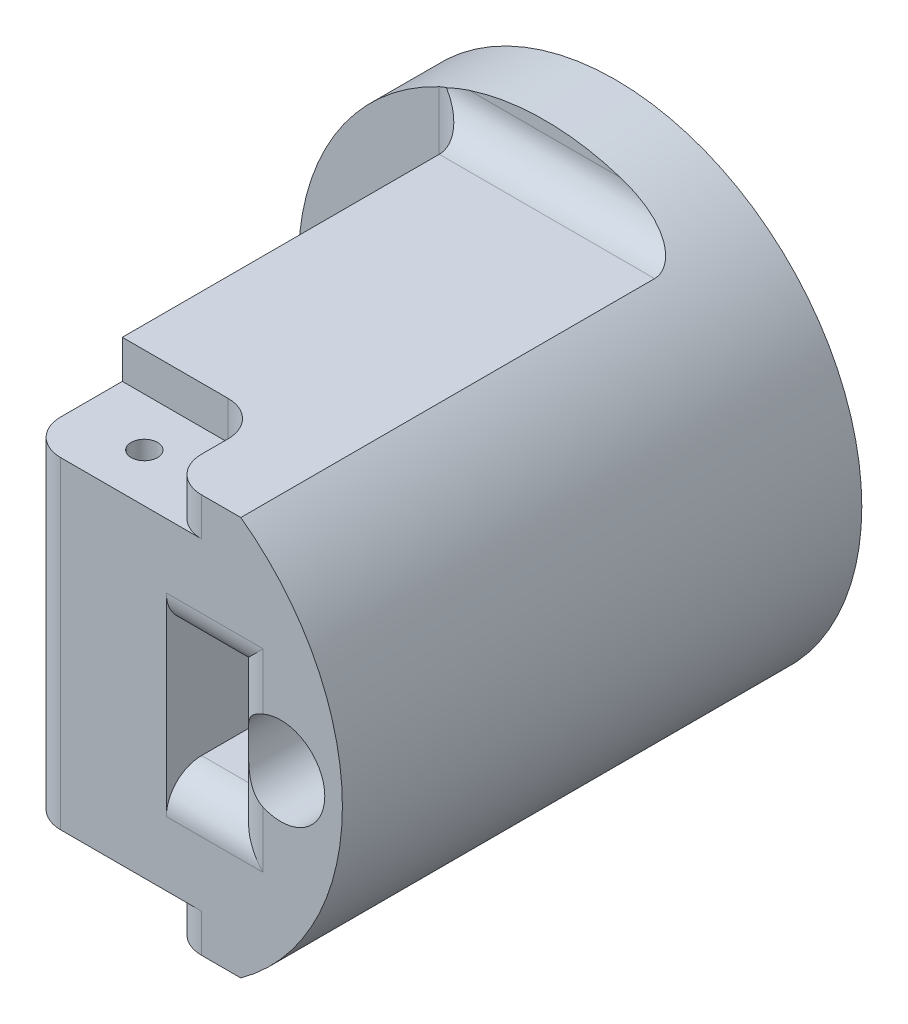
SolidWorks part; units mm, degrees
ref_plane "Front Plane" through (0, 0, 0) normal (0, 0, 1) x (1, 0, 0)
ref_plane "Top Plane" through (0, 0, 0) normal (0, 1, 0) x (1, 0, 0)
ref_plane "Right Plane" through (0, 0, 0) normal (1, 0, 0) x (0, 0, -1)
sketch "Sketch2" plane through (0, 0, 0) normal (0, 0, 1) x (1, 0, 0)
  circle A0 centre (0, 0) radius 14
  dimension "D1" = 28
extrude "Boss-Extrude1" add sketch "Sketch2" along normal blind 4
sketch "Sketch1" plane through (0, 0, 4) normal (0, 0, 1) x (1, 0, 0)
  line L0 (0, 14) -> (0, 11.775) construction
  line L1 (-3, 9.2) -> (3, 9.2)
  line L2 (-3, 9.2) -> (-3, -9.2)
  line L3 (-3, -9.2) -> (3, -9.2)
  line L4 (3, 9.2) -> (3, -9.2)
  line L5 (0, -9.2) -> (0, 9.2) construction
  line L6 (-3, 0) -> (3, 0) construction
  line L7 (-4, -11.325) -> (4, -11.325)
  line L8 (-4, -11.325) -> (-4, 11.325)
  line L9 (-4, 11.325) -> (4, 11.325)
  line L10 (4, -11.325) -> (4, 11.325)
  line L11 (0, 11.325) -> (0, -11.325) construction
  line L12 (-4, 0) -> (4, 0) construction
  line L13 (-2.5, 11.775) -> (2.5, 11.775)
  line L14 (-2.5, 11.775) -> (-2.5, 13.775)
  line L15 (2.5, 11.775) -> (2.5, 13.775)
  circle A0 centre (0, 0) radius 14 construction
  circle A1 centre (0, 0) radius 14
  point P0 (0, 0)
  point P4 (0, 0)
  point P8 (0, 14)
  point P17 (0, 11.775)
  point P21 (-2.5, -13.775)
  dimension "D1" = 6
  dimension "D2" = 18.4
  dimension "D3" = 5
  dimension "D4" = 2
  dimension "D5" = 0.45
  dimension "D6" = 1
  dimension "D7" = 2.45
extrude "Boss-Extrude2" add sketch "Sketch1" along normal blind 18 contours L7 L10 L9 L8 L1 L4 L3 L2 | L15 L13 L14
sketch "Sketch3" plane through (0, 0, 22) normal (0, 0, 1) x (1, 0, 0)
  line L4 (-4, -11.325) -> (4, -11.325)
  line L5 (4, -11.325) -> (4, 11.325)
  line L6 (4, 11.325) -> (-4, 11.325)
  line L7 (-4, 11.325) -> (-4, -11.325)
  line L8 (-4, -11.325) -> (4, -11.325)
  line L9 (4, -11.325) -> (4, 11.325)
  line L10 (4, 11.325) -> (-4, 11.325)
  line L11 (-4, 11.325) -> (-4, -11.325)
  dimension "D1" = 0
extrude "Boss-Extrude3" add sketch "Sketch3" along normal blind 2
sketch "Sketch4" plane through (0, 0, 4) normal (0, 0, 1) x (1, 0, 0)
  line L4 (3, -9.2) -> (3, 9.2)
  line L5 (3, 9.2) -> (-3, 9.2)
  line L6 (-3, 9.2) -> (-3, -9.2)
  line L7 (-3, -9.2) -> (3, -9.2)
  line L8 (3, -9.2) -> (3, 9.2)
  line L9 (3, 9.2) -> (-3, 9.2)
  line L10 (-3, 9.2) -> (-3, -9.2)
  line L11 (-3, -9.2) -> (3, -9.2)
  dimension "D1" = 0
extrude "Cut-Extrude1" cut sketch "Sketch4" against normal through all
sketch "Sketch5" plane through (3, 0, 0) normal (-1, 0, 0) x (0, 0, 1)
  line L0 (17, 9.2) -> (17, -9.2)
  line L4 (22, 9.2) -> (0, 9.2)
  line L5 (0, 9.2) -> (0, -9.2)
  line L6 (0, -9.2) -> (22, -9.2)
  line L7 (22, -9.2) -> (22, 9.2)
  line L8 (22, 9.2) -> (0, 9.2)
  line L9 (0, 9.2) -> (0, -9.2)
  line L10 (0, -9.2) -> (22, -9.2)
  line L11 (22, -9.2) -> (22, 9.2)
  line M6 (22, 9.2) -> (0, 9.2)
  line M8 (0, -9.2) -> (22, -9.2)
  line M9 (22, -9.2) -> (22, 9.2)
  dimension "D2" = 5
  dimension "D1" = 0
extrude "Cut-Extrude2" cut sketch "Sketch5" along normal through all contours L0 M6 M8 M9
sketch "Sketch6" plane through (0, 0, 24) normal (0, 0, 1) x (1, 0, 0)
  line L4 (-4, 11.325) -> (-4, -11.325)
  line L5 (-4, -11.325) -> (4, -11.325)
  line L6 (4, -11.325) -> (4, 11.325)
  line L7 (4, 11.325) -> (-4, 11.325)
  line L8 (-4, 11.325) -> (-4, -11.325)
  line L9 (-4, -11.325) -> (4, -11.325)
  line L10 (4, -11.325) -> (4, 11.325)
  line L11 (4, 11.325) -> (-4, 11.325)
  dimension "D1" = 0
sketch "Sketch11" plane through (0, 0, 24) normal (0, 0, 1) x (1, 0, 0)
  line L0 (4, -11.325) -> (4, 11.325) construction
  line L1 (-4, -9.1553) -> (4, -9.1553)
  line L2 (-4, -9.1553) -> (-4, 9.1553)
  line L3 (-4, 9.1553) -> (4, 9.1553)
  line L4 (4, -9.1553) -> (4, 9.1553)
  line L5 (0, 9.1553) -> (0, -9.1553) construction
  line L6 (-4, 0) -> (4, 0) construction
  circle A0 centre (0, 0) radius 13.75 construction
  point P0 (0, 0)
  point P9 (-4, 13.1553)
  dimension "D1" = 27.5
  dimension "D2" = 4
extrude "Boss-Extrude5" add sketch "Sketch11" along normal blind 5.5
sketch "Sketch8" plane through (0, 0, 4) normal (0, 0, 1) x (1, 0, 0)
  line L0 (4, -11.325) -> (4, 11.325) construction
  line L1 (4, -11.325) -> (4, 11.325)
  line L2 (4, 11.325) -> (8.2307, 11.325)
  line L3 (4, -11.325) -> (8.2307, -11.325)
  circle A0 centre (0, 0) radius 14 construction
  circle A1 centre (0, 0) radius 14
  circle M1 centre (0, 0) radius 14
  line M2 (4, 11.325) -> (4, -11.325)
extrude "Boss-Extrude4" add sketch "Sketch8" along normal up to surface (25.5 mm away) contours L3 L2 M2 M1
sketch "Sketch9" plane through (0, 0, 24) normal (0, 0, 1) x (1, 0, 0)
  line L0 (4, -11.325) -> (4, 11.325) construction
  line L1 (4, -11.325) -> (4, 11.325)
  line L2 (4, 3.5) -> (4, -3.5)
  line L3 (4, 3.5) -> (7.5, 3.5)
  line L4 (4, -3.5) -> (7.5, -3.5)
  line L5 (7.5, 3.5) -> (7.5, -3.5)
  line L6 (4, -3.5) -> (4, 3.5)
  point P2 (4, 0)
  point P3 (4, -3.5)
  point P4 (4, 3.5)
  point P13 (4, 0)
  dimension "D1" = 7
  dimension "D3" = 3.5
extrude "Cut-Extrude4" cut sketch "Sketch9" against normal blind 6 from surface at 5.5 contours L5 L3 L1 L4 starting at face at (3.7788, 0, 29.5)
sketch "Sketch7" plane through (0, -9.1553, 0) normal (0, 1, 0) x (1, 0, 0)
  line L1 (-4, -29.5) -> (4, -29.5)
  line L2 (0, -29.5) -> (0, -26.75) construction
  line L3 (4, -29.5) -> (-4, -29.5) construction
  circle A0 centre (0, -26.75) radius 0.75
  dimension "D2" = 1.5
  dimension "D1" = 2.75
extrude "Cut-Extrude5" cut sketch "Sketch7" along normal through all
fillet "Fillet3" radius 1 3 edges at (-4, -9.2, 19.5) (-4, 0, 17) (-4, 9.2, 19.5)
fillet "Fillet4" radius 2 3 edges at (2.1154, -11.325, 4) (2.1154, 11.325, 4) (-4, 0, 4)
fillet "Fillet5" radius 2 1 edges at (3, 0, 22)
sketch "Sketch12" plane through (0, 0, 29.5) normal (0, 0, 1) x (1, 0, 0)
  line L0 (0, 0) -> (0, 14) construction
  line L1 (14, 0) -> (10.5, 0) construction
  arc A0 (-6, 12.6491) -> (-6, -12.6491) centre (0, 0) ccw construction
  arc A1 (-6, 12.6491) -> (-6, -12.6491) centre (0, 0) ccw
  arc A2 (8.2307, -11.325) -> (8.2307, 11.325) centre (0, 0) ccw construction
  arc A3 (8.2307, -11.325) -> (8.2307, 11.325) centre (0, 0) ccw
  arc A4 (4.2948, 13.325) -> (-4.2948, 13.325) centre (0, 0) ccw construction
  arc A5 (4.2948, 13.325) -> (-4.2948, 13.325) centre (0, 0) ccw
  circle A6 centre (10.5, 0) radius 2.5
  point P3 (-14, 0)
  point P6 (14, 0)
  point P15 (13, 0)
  dimension "D1" = 5
  dimension "D2" = 1
sketch "Sketch14" plane through (0, 0, 0) normal (0, 1, 0) x (1, 0, 0)
  line L1 (-13.998, -2) -> (-5.9985, -2) construction
  line L2 (10.5, -29.5) -> (10.5, -2)
  line L3 (10.5, -2) -> (13, -2)
  line L4 (13, -2) -> (13, -29.5)
  line L5 (8.2307, -29.5) -> (14, -29.5) construction
  line L6 (13, -29.5) -> (10.5, -29.5)
  line L7 (12, -2) -> (13, -3.6)
  line L8 (12, -2) -> (12, 0)
  line L9 (14, 0) -> (-14, 0) construction
  line L10 (12, 0) -> (10.5, 0)
  line L11 (10.5, 0) -> (10.5, -2)
  point P0 (10.5, -29.5)
  dimension "D1" = 2.5
  dimension "D2" = 1.6
  dimension "D3" = 1.5
  dimension "D4" = 2
revolve "Cut-Revolve1" cut sketch "Sketch14" angle 360 about L2
mirror "Mirror1" about plane through (0, 0, 0) normal (1, 0, 0) of "Cut-Revolve1"
fillet "Fillet6" radius 2 6 edges at (5.75, 3.5, 29.5) (7.5, 0, 29.5) (5.75, -3.5, 29.5) (4, -10.2401, 24) (4, 10.2401, 24) (-4, 0, 29.5)
